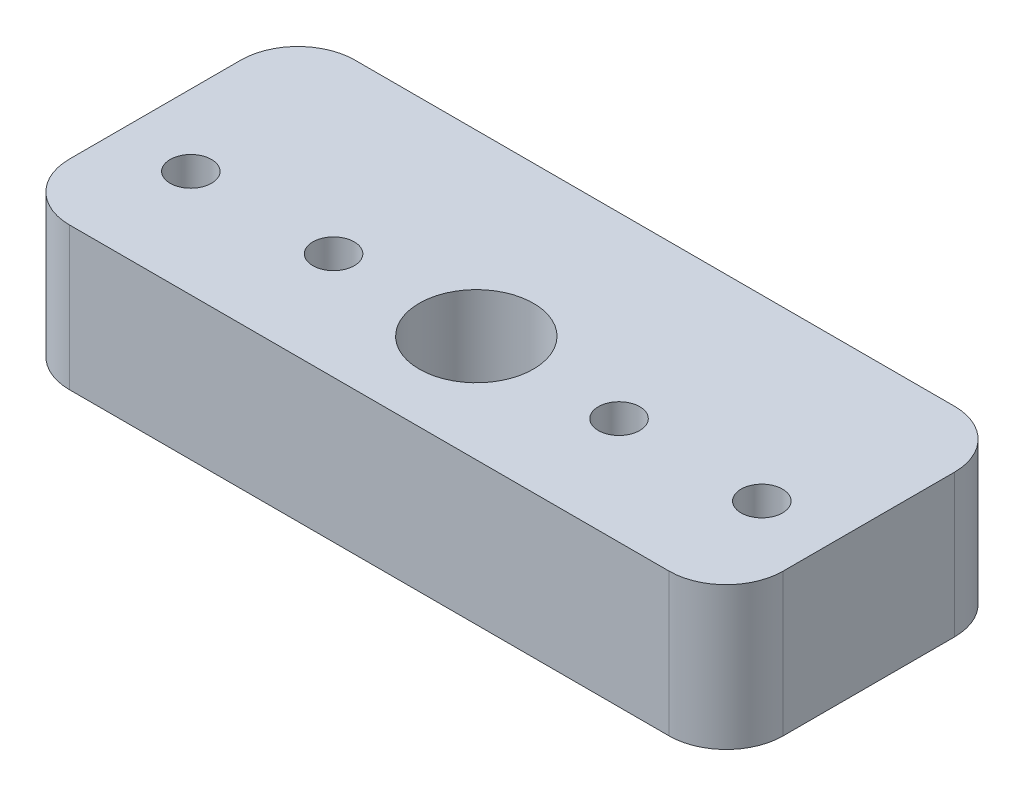
SolidWorks part; units mm, degrees
ref_plane "Front Plane" through (0, 0, 0) normal (0, 0, 1) x (1, 0, 0)
ref_plane "Top Plane" through (0, 0, 0) normal (0, 1, 0) x (1, 0, 0)
ref_plane "Right Plane" through (0, 0, 0) normal (1, 0, 0) x (0, 0, -1)
sketch "Sketch1" plane through (0, 0, 0) normal (0, 1, 0) x (1, 0, 0)
  line L0 (-25, -2.5) -> (25, -2.5) construction
  line L1 (-21, 10) -> (21, 10)
  line L2 (-25, 6) -> (-25, -6)
  line L3 (-21, -10) -> (21, -10)
  line L4 (25, 6) -> (25, -6)
  line L5 (-25, 10) -> (25, -10) construction
  line L6 (-25, -10) -> (25, 10) construction
  line L7 (0, -10) -> (0, 10) construction
  line L8 (25, 10) -> (-25, -10) construction
  arc A0 (-25, -6) -> (-21, -10) centre (-21, -6) ccw
  arc A1 (21, -10) -> (25, -6) centre (21, -6) ccw
  arc A2 (21, 10) -> (25, 6) centre (21, 6) cw
  arc A3 (-21, 10) -> (-25, 6) centre (-21, 6) ccw
  circle A4 centre (0, -2.5) radius 4
  circle A5 centre (10, -2.5) radius 1.45
  circle A6 centre (20, -2.5) radius 1.45
  circle A7 centre (-20, -2.5) radius 1.45
  circle A8 centre (-10, -2.5) radius 1.45
  point P0 (0, 0)
  dimension "D3" = 4
  dimension "D4" = 8
  dimension "D5" = 2.9
  dimension "D6" = 2.9
  dimension "D1" = 20
  dimension "D7" = 7.5
  dimension "D8" = 10
  dimension "D9" = 40
  dimension "D2" = 5
extrude "Boss-Extrude1" add sketch "Sketch1" along normal blind 10
equation "\"Y-ROD-SPACING\"=75"
equation "\"Y-BED-OFFSET\"=2"
equation "\"Y-BED-ROD-INSET\"=3.5"
equation "\"T-SLOT-NUT-FILLET-RADIUS\"=0.5"
equation "\"T-SLOT-SCREW-SHAFT-RADIUS\"=1.55"
equation "\"T-SLOT-SCREW-SHAFT-CUTOUT-LENGTH\"=11"
equation "\"T-SLOT-NUT-DEPTH\"=3.5"
equation "\"T-SLOT-NUT-WIDTH\"=2.85"
equation "\"T-SLOT-NUT-END-DISTANCE\"=8"
equation "\"ACRYLIC-TAB-CUTOUT-SIZE\"=\"ACRYLIC-THICKNESS\"+\"ACRYLIC-TAB-TOLERANCE\"*2"
equation "\"ACRYLIC-M3-HOLE\"=2.9"
equation "\"SMOOTHROD-CAP-SCREW-DISTANCE\"=20"
equation "\"D5@Sketch1\"=\"ACRYLIC-M3-HOLE\""
equation "\"D6@Sketch1\"=\"ACRYLIC-M3-HOLE\""
equation "\"D8@Sketch1\"=\"SMOOTHROD-CAP-SCREW-DISTANCE\"/2"
equation "\"ACRYLIC-TAB-WIDTH\"=\"ACRYLIC-THICKNESS\""
equation "\"FRAME-WIDTH-INNER\"=370"
equation "\"NEMA17-HOLE-SPACING\"=31"
equation "\"NEMA17-CENTRAL-CUTOUT\"=22.5"
equation "\"Z-BRACKET-REACH\"=57"
equation "\"TOP-BRACKET-SPACING\"=40"
equation "\"D9@Sketch1\"=\"TOP-BRACKET-SPACING\""
equation "\"D2@Sketch1\"=\"ACRYLIC-TAB-WIDTH\"/2"
equation "\"X-ROD-SPACING\"=45"
equation "\"Z-ROD-SPACING\"=17.5"
equation "\"ACRYLIC-THICKNESS\"=10"
equation "\"ACRYLIC-THICKNESS2\"=4.5"
equation "\"SMOOTHROD-X-LENGTH\"=350"
equation "\"SMOOTHROD-Y-LENGTH\"=350"
equation "\"SMOOTHROD-Z-LENGTH\"=350"
equation "\"SMOOTHROD-TIGHTENING-HEADROOM\"=.25"
equation "\"LEADSCREW-Z-LENGTH\"=300"
equation "\"SCREW-LENGTH-FRAME\"=\"ACRYLIC-THICKNESS\" + 10"
equation "\"SCREW-HEAD-RADIUS\"=6"
equation "\"PRINTED-X-SMOOTHROD-DIAMETER\"=8.8"
equation "\"PRINTED-X-SMOOTHROD-CUTOUT\"=10"
equation "\"PRINTED-X-BASE-HEIGHT\"=10"
equation "\"PRINTED-LM8UU-CUTOUT-SIZE\"=15.5"
equation "\"PRINTED-LM8UU-CUTOUT-LENGTH\"=24.5"
equation "\"PRINTED-X-IDLER-HEIGHT\"=16"
equation "\"PSU-MOUNTING-WIDTH\"=95"
equation "\"PSU-MOUNTING-HEIGHT\"=177"
equation "\"D1@Boss-Extrude1\"=\"ACRYLIC-THICKNESS\""
